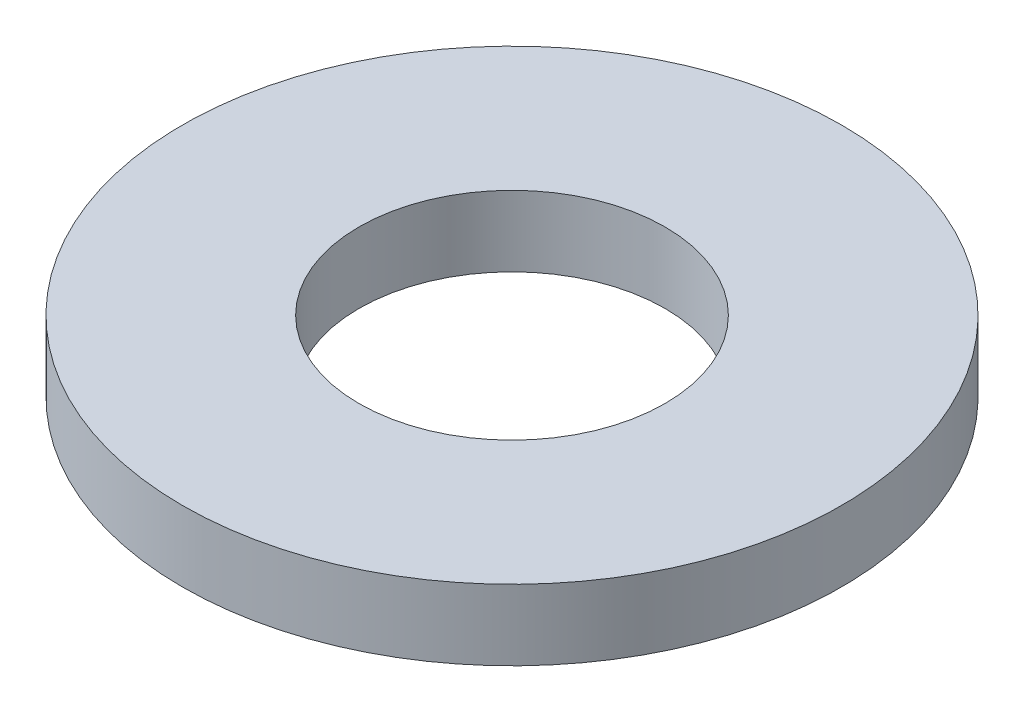
SolidWorks part; units mm, degrees
ref_plane "Front Plane" through (0, 0, 0) normal (0, 0, 1) x (1, 0, 0)
ref_plane "Top Plane" through (0, 0, 0) normal (0, 1, 0) x (1, 0, 0)
ref_plane "Right Plane" through (0, 0, 0) normal (1, 0, 0) x (0, 0, -1)
sketch "Sketch1" plane through (0, 0, 0) normal (0, 1, 0) x (1, 0, 0)
  circle A0 centre (0, 0) radius 70
  dimension "FLANGE_OD" = 140
extrude "Boss-Extrude1" add sketch "Sketch1" along normal blind 15
sketch "Sketch2" plane through (0, 0, 0) normal (0, 1, 0) x (1, 0, 0)
  circle A0 centre (0, 0) radius 32.5
  dimension "BORE_D" = 65
extrude "Cut-Extrude1" cut sketch "Sketch2" along normal through all
sketch "Sketch3" plane through (0, 15, 0) normal (0, 1, 0) x (1, 0, 0)
  circle A0 centre (0, 0) radius 24.7268 construction
  circle A1 centre (-24.7268, 0) radius 4.3055
  dimension "BOLT_D" = 8.611
  dimension "BOLT_PCD" = 49.4536
extrude "Cut-Extrude2" cut sketch "Sketch3" against normal blind 12.8897 rebuild error yes
pattern_circular "CirPattern1" count 3 over 360 rebuild error yes
